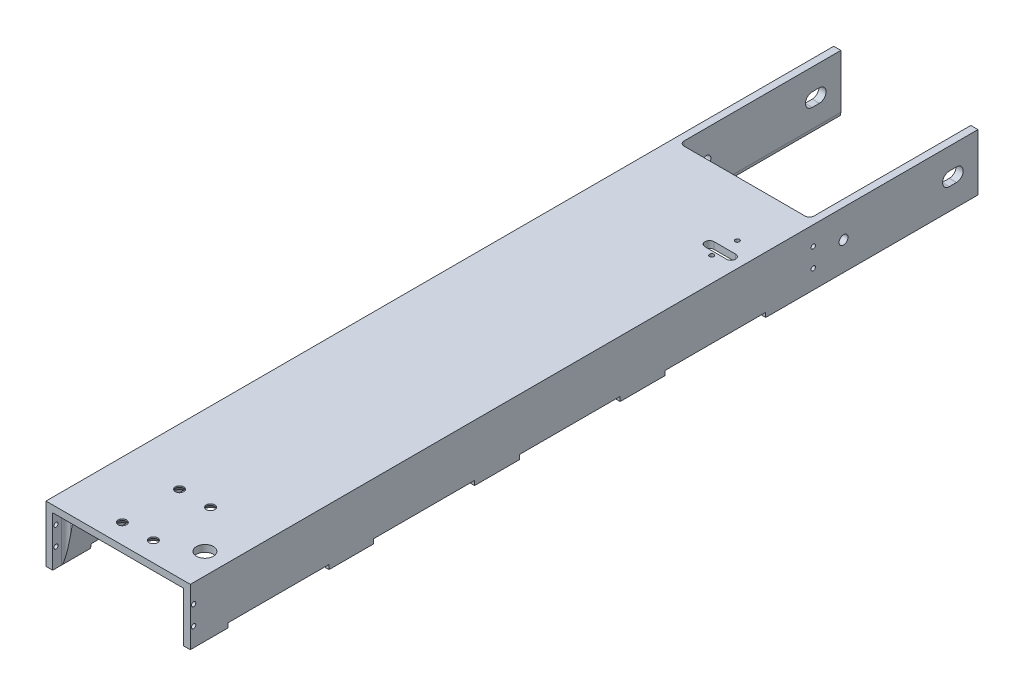
SolidWorks part; units mm, degrees
ref_plane "Front Plane" through (0, 0, 0) normal (0, 0, 1) x (1, 0, 0)
ref_plane "Top Plane" through (0, 0, 0) normal (0, 1, 0) x (1, 0, 0)
ref_plane "Right Plane" through (0, 0, 0) normal (1, 0, 0) x (0, 0, -1)
sketch "Sketch1" plane through (0, 0, 0) normal (0, 0, 1) x (1, 0, 0)
  line L0 (-51.1048, 0) -> (51.1048, 0)
  line L1 (51.1048, 0) -> (51.1048, -40.132)
  line L2 (51.1048, -40.132) -> (46.4058, -40.132)
  line L3 (46.4058, -40.132) -> (41.2191, -10.0709)
  line L4 (34.9616, -4.8006) -> (-34.9616, -4.8006)
  line L5 (-41.2191, -10.0709) -> (-46.4058, -40.132)
  line L6 (-46.4058, -40.132) -> (-51.1048, -40.132)
  line L7 (-51.1048, -40.132) -> (-51.1048, 0)
  arc A0 (-34.9616, -4.8006) -> (-41.2191, -10.0709) centre (-34.9616, -11.1506) ccw
  arc A1 (41.2191, -10.0709) -> (34.9616, -4.8006) centre (34.9616, -11.1506) ccw
  point P8 (0, 0)
  point P12 (-40.3098, -4.8006)
  point P15 (40.3098, -4.8006)
  dimension "D7" = 6.35
  dimension "D1" = 40.132
  dimension "D2" = 4.699
  dimension "D3" = 4.8006
  dimension "D4" = 102.2096
  dimension "D5" = 10.795
  dimension "D6" = 10.795
extrude "Boss-Extrude1" add sketch "Sketch1" along normal blind 558.0063
sketch "Sketch3" plane through (0, 0, 0) normal (0, 1, 0) x (1, 0, 0)
  line L0 (51.1048, 0) -> (-51.1048, 0) construction
  line L1 (-42.8625, -114.3) -> (42.8625, -114.3)
  line L2 (-46.0375, -111.125) -> (-46.0375, 0)
  line L3 (-46.0375, 0) -> (46.0375, 0)
  line L4 (46.0375, -111.125) -> (46.0375, 0)
  line L5 (-46.0375, -114.3) -> (46.0375, 0) construction
  line L6 (-46.0375, 0) -> (46.0375, -114.3) construction
  line L7 (-34.9616, -558.0063) -> (34.9616, -558.0063) construction
  line L9 (26.3398, -165.4336) -> (41.5798, -165.4336) construction
  line L10 (26.3398, -162.2586) -> (41.5798, -162.2586)
  line L11 (26.3398, -168.6086) -> (41.5798, -168.6086)
  line L12 (0, -1000) -> (0, 49000) construction
  line L13 (51.1048, -558.0063) -> (-51.1048, -558.0063) construction
  line L15 (51.1048, -558.0063) -> (51.1048, 0) construction
  line L16 (-46.0375, -161.1156) -> (46.0375, -161.1156) construction
  arc A0 (26.3398, -162.2586) -> (26.3398, -168.6086) centre (26.3398, -165.4336) ccw
  arc A1 (41.5798, -168.6086) -> (41.5798, -162.2586) centre (41.5798, -165.4336) ccw
  circle A2 centre (33.9598, -153.3686) radius 1.524
  circle A3 centre (33.9598, -171.5296) radius 1.524
  circle A4 centre (-11.0109, -544.0362) radius 3
  circle A5 centre (11.0109, -503.5232) radius 3
  circle A6 centre (-11.0109, -503.5232) radius 3
  circle A7 centre (11.0109, -544.0362) radius 3
  circle A8 centre (36.0486, -532.6063) radius 6
  arc A9 (-42.8625, -114.3) -> (-46.0375, -111.125) centre (-42.8625, -111.125) cw
  arc A10 (42.8625, -114.3) -> (46.0375, -111.125) centre (42.8625, -111.125) ccw
  point P0 (0, -57.15)
  point P13 (33.9598, -165.4336)
  dimension "D2" = 6.35
  dimension "D6" = 3.048
  dimension "D9" = 6
  dimension "D13" = 12
  dimension "D17" = 3.175
  dimension "D1" = 114.3
  dimension "D3" = 15.24
  dimension "D4" = 9.525
  dimension "D5" = 1.143
  dimension "D7" = 2.921
  dimension "D8" = 8.89
  dimension "D10" = 40.513
  dimension "D11" = 22.0218
  dimension "D12" = 13.97
  dimension "D14" = 15.0562
  dimension "D15" = 25.4
  dimension "D16" = 92.075
extrude "Cut-Extrude1" cut sketch "Sketch3" against normal through all
sketch "Sketch4" plane through (51.1048, 0, 0) normal (1, 0, 0) x (0, 0, -1)
  line L0 (-15.24, -20.066) -> (-20.32, -20.066) construction
  line L1 (-15.24, -24.8285) -> (-20.32, -24.8285)
  line L2 (-15.24, -15.3035) -> (-20.32, -15.3035)
  line L3 (0, -40.132) -> (0, 0) construction
  line L4 (-150.368, -40.132) -> (-150.368, -36.957)
  line L5 (-558.0063, -40.132) -> (0, -40.132) construction
  line L6 (-150.368, -36.957) -> (-221.8055, -36.957)
  line L7 (-221.8055, -36.957) -> (-221.8055, -40.132)
  line L8 (-221.8055, -40.132) -> (-150.368, -40.132)
  line L9 (-156.3531, 0) -> (-111.9031, 0) construction
  line L11 (-558.0063, -40.132) -> (-558.0063, 0) construction
  line L12 (-558.0063, 0) -> (0, 0) construction
  line L21 (-253.492, -40.132) -> (-253.492, -36.957)
  line L22 (-253.492, -36.957) -> (-324.9295, -36.957)
  line L23 (-324.9295, -36.957) -> (-324.9295, -40.132)
  line L24 (-324.9295, -40.132) -> (-253.492, -40.132)
  line L25 (-356.616, -40.132) -> (-356.616, -36.957)
  line L26 (-356.616, -36.957) -> (-428.0535, -36.957)
  line L27 (-428.0535, -36.957) -> (-428.0535, -40.132)
  line L28 (-428.0535, -40.132) -> (-356.616, -40.132)
  line L29 (-459.74, -40.132) -> (-459.74, -36.957)
  line L30 (-459.74, -36.957) -> (-531.1775, -36.957)
  line L31 (-531.1775, -36.957) -> (-531.1775, -40.132)
  line L32 (-531.1775, -40.132) -> (-459.74, -40.132)
  arc A0 (-15.24, -24.8285) -> (-15.24, -15.3035) centre (-15.24, -20.066) ccw
  arc A1 (-20.32, -15.3035) -> (-20.32, -24.8285) centre (-20.32, -20.066) ccw
  circle A2 centre (-95.25, -20.066) radius 3.175
  circle A3 centre (-116.6813, -26.8224) radius 1.524
  circle A4 centre (-116.6812, -13.4112) radius 1.524
  circle A5 centre (-555.625, -13.4112) radius 1.524
  circle A6 centre (-555.625, -26.8224) radius 1.524
  point P3 (-17.78, -20.066)
  point P10 (0, -20.066)
  dimension "D3" = 9.525
  dimension "D5" = 6.35
  dimension "D10" = 3.048
  dimension "D14" = 3.048
  dimension "D1" = 5.08
  dimension "D2" = 15.24
  dimension "D4" = 95.25
  dimension "D6" = 3.175
  dimension "D7" = 71.4375
  dimension "D8" = 150.368
  dimension "D11" = 13.4112
  dimension "D12" = 13.4112
  dimension "D13" = 116.6813
  dimension "D15" = 2.3813
  dimension "D16" = 13.4112
  dimension "D17" = 13.4112
  dimension "D9" = 4
extrude "Cut-Extrude2" cut sketch "Sketch4" against normal through all
chamfer "Chamfer1" distance 3.8862 angle 42 4 edges at (8.0109, -4.8006, 503.5232) (8.0109, -4.8006, 544.0362) (-14.0109, -4.8006, 544.0362) (-14.0109, -4.8006, 503.5232) first distance on face at (14.0109, 0, 503.5232) first distance on face at (14.0109, 0, 544.0362) first distance on face at (-14.0109, 0, 544.0362) first distance on face at (-14.0109, 0, 503.5232)
sketch "Sketch5" plane through (0, -40.132, 0) normal (0, -1, 0) x (1, 0, 0)
  line L0 (-51.1048, 150.368) -> (-51.1048, 221.8055) construction
  line L1 (31.3779, 146.05) -> (42.5958, 146.05)
  line L2 (31.3779, 146.05) -> (31.3779, 177.8)
  line L3 (31.3779, 177.8) -> (42.5958, 177.8)
  line L4 (46.4058, 149.86) -> (46.4058, 173.99)
  line L5 (31.3779, 146.05) -> (46.4058, 177.8) construction
  line L6 (31.3779, 177.8) -> (46.4058, 146.05) construction
  line L7 (46.4058, 558.0063) -> (46.4058, 531.1775) construction
  line L8 (-56.5438, 388.0168) -> (-40.0893, 388.0168) construction
  line L9 (51.1048, 150.368) -> (51.1048, 221.8055) construction
  line L10 (-42.2275, 221.0689) -> (-29.5583, 221.0689)
  line L11 (-46.0375, 217.2589) -> (-46.0375, 102.0788)
  line L12 (-42.2275, 98.2688) -> (-29.5583, 98.2688)
  line L13 (-29.5583, 221.0689) -> (-29.5583, 98.2688)
  line L16 (-41.9227, 217.2589) -> (10.0965, 217.2589) construction
  line L19 (46.4058, 558.0063) -> (32.5205, 558.0063)
  line L20 (46.4058, 558.0063) -> (46.4058, 513.5563)
  line L21 (43.2308, 510.3813) -> (32.5205, 510.3813)
  line L22 (32.5205, 558.0063) -> (32.5205, 510.3813)
  line L24 (-46.4058, 558.0063) -> (-34.8231, 558.0063)
  line L25 (-46.4058, 558.0063) -> (-46.4058, 551.6563)
  line L26 (-43.2308, 548.4813) -> (-34.8231, 548.4813)
  line L27 (-34.8231, 558.0063) -> (-34.8231, 548.4813)
  line L28 (42.8625, 123.825) -> (32.685, 123.825)
  line L29 (46.0375, 120.65) -> (46.0375, 102.6149)
  line L30 (46.0375, 102.6149) -> (32.685, 102.6149)
  line L31 (32.685, 123.825) -> (32.685, 102.6149)
  line L33 (-46.0375, 0) -> (-46.0375, 111.125) construction
  line L34 (46.0375, 111.125) -> (46.0375, 0) construction
  arc A0 (42.5958, 177.8) -> (46.4058, 173.99) centre (42.5958, 173.99) cw
  arc A1 (42.5958, 146.05) -> (46.4058, 149.86) centre (42.5958, 149.86) ccw
  arc A2 (-46.0375, 102.0788) -> (-42.2275, 98.2688) centre (-42.2275, 102.0788) ccw
  arc A3 (-42.2275, 221.0689) -> (-46.0375, 217.2589) centre (-42.2275, 217.2589) ccw
  arc A4 (46.4058, 513.5563) -> (43.2308, 510.3813) centre (43.2308, 513.5563) cw
  arc A5 (-46.4058, 551.6563) -> (-43.2308, 548.4813) centre (-43.2308, 551.6563) ccw
  arc A6 (42.8625, 123.825) -> (46.0375, 120.65) centre (42.8625, 120.65) cw
  circle A7 centre (-48.7235, 186.0867) radius 1.1303
  circle A8 centre (-48.7236, 284.8928) radius 1.1303
  circle A9 centre (-48.7236, 391.1918) radius 1.1303
  circle A10 centre (-48.7236, 491.7745) radius 1.1303
  circle A11 centre (48.7236, 186.0867) radius 1.1303
  circle A12 centre (48.7235, 284.8928) radius 1.1303
  circle A13 centre (48.7235, 383.6988) radius 1.1303
  circle A14 centre (48.7235, 482.5048) radius 1.1303
  point P0 (38.8919, 161.925)
  point P16 (-51.1048, 186.0867)
  point P55 (46.4058, 123.825)
  point P58 (51.1048, 186.0867)
  dimension "D3" = 3.81
  dimension "D4" = 3.175
  dimension "D6" = 3.175
  dimension "D7" = 3.175
  dimension "D9" = 2.2606
  dimension "D13" = 2.2606
  dimension "D1" = 31.75
  dimension "D2" = 146.05
  dimension "D5" = 44.45
  dimension "D8" = 6.35
  dimension "D10" = 2.3813
  dimension "D12" = 2.3813
  dimension "D11" = 3.175
  dimension "D14" = 4
extrude "Cut-Extrude3" cut sketch "Sketch5" against normal up to surface (35.3314 mm away) up to face at (4.5117, -4.8006, 503.5232)
sketch "Sketch6" plane through (-51.1048, 0, 0) normal (-1, 0, 0) x (0, 0, 1)
  line L0 (558.0063, 0) -> (558.0063, -40.132) construction
  line L1 (402.4313, -25.4) -> (446.8813, -25.4)
  line L2 (399.2563, -22.225) -> (399.2563, -15.875)
  line L3 (402.4313, -12.7) -> (446.8813, -12.7)
  line L4 (450.0563, -22.225) -> (450.0563, -15.875)
  line L5 (558.0063, 0) -> (0, 0) construction
  circle A0 centre (200.8251, -23.3045) radius 1.5494
  circle A1 centre (162.7759, -23.3045) radius 1.5494
  circle A2 centre (136.6393, -23.3045) radius 1.5494
  circle A3 centre (396.0813, -9.525) radius 1.1303
  circle A4 centre (162.7759, -23.3045) radius 1.27 construction
  circle A5 centre (136.6393, -23.3045) radius 1.27 construction
  circle A6 centre (200.8251, -23.3045) radius 1.27 construction
  circle A7 centre (453.2313, -9.525) radius 1.1303
  circle A8 centre (453.2313, -28.575) radius 1.1303
  circle A9 centre (396.0813, -28.575) radius 1.1303
  arc A10 (446.8813, -12.7) -> (450.0563, -15.875) centre (446.8813, -15.875) cw
  arc A11 (446.8813, -25.4) -> (450.0563, -22.225) centre (446.8813, -22.225) ccw
  arc A12 (402.4313, -25.4) -> (399.2563, -22.225) centre (402.4313, -22.225) cw
  arc A13 (399.2563, -15.875) -> (402.4313, -12.7) centre (402.4313, -15.875) cw
  point P30 (450.0563, -12.7)
  point P35 (399.2563, -25.4)
  point P38 (399.2563, -12.7)
  dimension "D1" = 3.0988
  dimension "D6" = 2.2606
  dimension "D11" = 3.175
  dimension "D2" = 107.95
  dimension "D3" = 50.8
  dimension "D4" = 12.7
  dimension "D5" = 12.7
  dimension "D7" = 3.175
  dimension "D8" = 3.175
  dimension "D9" = 3.175
  dimension "D10" = 3.175
extrude "Cut-Extrude7" cut sketch "Sketch6" against normal up to next
